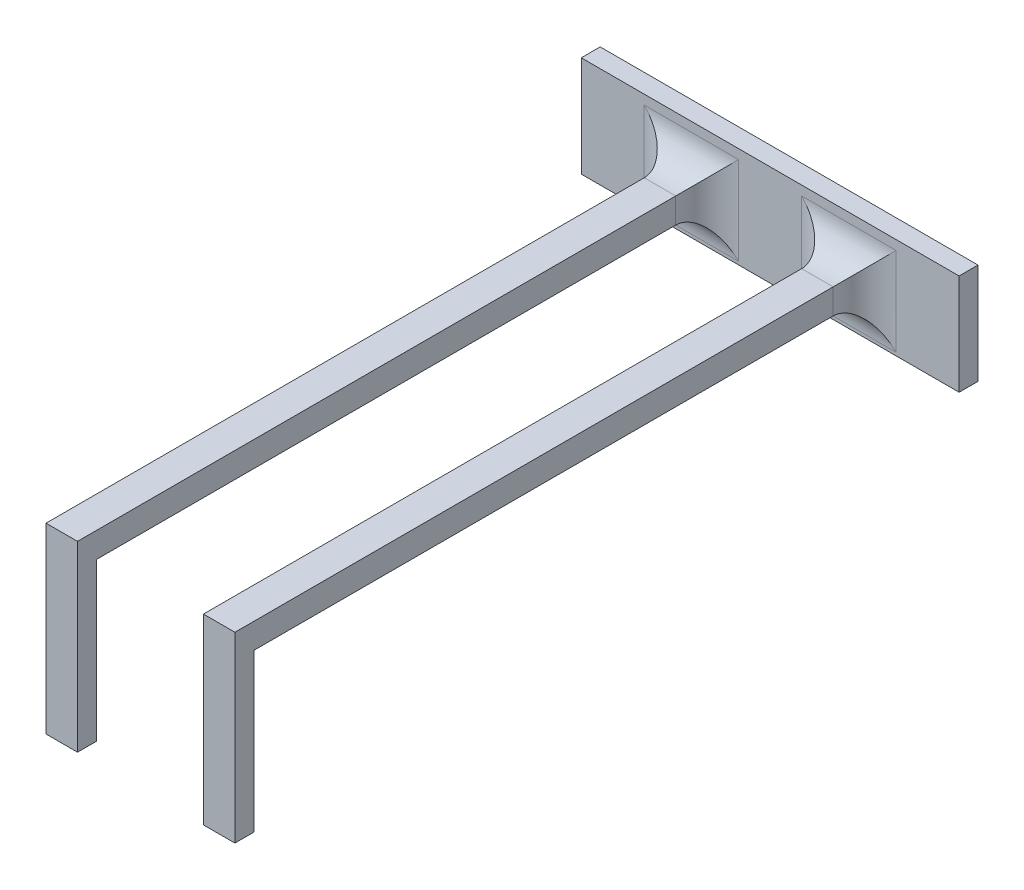
SolidWorks part; units mm, degrees
ref_plane "前视基准面" through (0, 0, 0) normal (0, 0, 1) x (1, 0, 0)
ref_plane "上视基准面" through (0, 0, 0) normal (0, 1, 0) x (1, 0, 0)
ref_plane "右视基准面" through (0, 0, 0) normal (1, 0, 0) x (0, 0, -1)
other "Configuration Table"
sketch "草图1" plane through (0, 0, 0) normal (0, 0, 1) x (1, 0, 0)
  line L1 (-22.149, 8.3709) -> (37.851, 8.3709)
  line L2 (-22.149, 8.3709) -> (-22.149, -7.6291)
  line L3 (-22.149, -7.6291) -> (37.851, -7.6291)
  line L4 (37.851, 8.3709) -> (37.851, -7.6291)
  dimension "D1" = 60
  dimension "D2" = 16
extrude "凸台-拉伸1" add sketch "草图1" along normal blind 3
sketch "草图2" plane through (0, 0, 3) normal (0, 0, 1) x (1, 0, 0)
  line L0 (-22.149, 8.3709) -> (-22.149, -7.6291) construction
  line L1 (-22.149, 1.8709) -> (37.851, 1.8709)
  line L2 (-22.149, 1.8709) -> (-22.149, -2.1291)
  line L3 (-22.149, -2.1291) -> (37.851, -2.1291)
  line L4 (37.851, 1.8709) -> (37.851, -2.1291)
  line L5 (37.851, -7.6291) -> (37.851, 8.3709) construction
  line L6 (-22.149, -7.6291) -> (37.851, -7.6291) construction
  dimension "D1" = 4
  dimension "D2" = 5.5
extrude "凸台-拉伸2" add sketch "草图2" along normal blind 100
sketch "草图3" plane through (0, -2.1291, 0) normal (0, -1, 0) x (1, 0, 0)
  line L0 (-22.149, 103) -> (37.851, 103) construction
  line L1 (-7.149, 103) -> (-2.149, 103)
  line L2 (-7.149, 103) -> (-7.149, 100)
  line L3 (-7.149, 100) -> (-2.149, 100)
  line L4 (22.851, 103) -> (22.851, 100)
  line L5 (-2.149, 103) -> (-2.149, 100)
  line L6 (17.851, 103) -> (17.851, 100)
  line L7 (17.851, 103) -> (22.851, 103)
  line L8 (17.851, 100) -> (22.851, 100)
  line L9 (-22.149, 103) -> (-22.149, 3) construction
  dimension "D1" = 20
  dimension "D2" = 30
  dimension "D3" = 5
  dimension "D4" = 3
  dimension "D5" = 15
extrude "凸台-拉伸3" add sketch "草图3" along normal blind 25
sketch "草图4" plane through (0, -2.1291, 0) normal (0, -1, 0) x (1, 0, 0)
  line L0 (-22.149, 3) -> (37.851, 3) construction
  line L1 (-22.149, 103) -> (-7.149, 103)
  line L2 (-22.149, 103) -> (-22.149, 3)
  line L3 (-22.149, 3) -> (-7.149, 3)
  line L4 (-7.149, 103) -> (-7.149, 3)
  line L5 (17.851, 103) -> (17.851, 100) construction
  line L6 (-2.149, 103) -> (17.851, 103)
  line L7 (-2.149, 103) -> (-2.149, 3)
  line L8 (-2.149, 3) -> (17.851, 3)
  line L9 (17.851, 103) -> (17.851, 3)
  line L10 (22.851, 103) -> (37.851, 103)
  line L11 (22.851, 103) -> (22.851, 3)
  line L12 (22.851, 3) -> (37.851, 3)
  line L13 (37.851, 103) -> (37.851, 3)
  line L14 (-7.149, 103) -> (-7.149, 100) construction
extrude "切除-拉伸1" cut sketch "草图4" against normal blind 30
fillet "圆角1" radius 5 8 edges at (20.351, 1.8709, 3) (22.851, -0.1291, 3) (20.351, -2.1291, 3) (17.851, -0.1291, 3) (-4.649, 1.8709, 3) (-2.149, -0.1291, 3) (-4.649, -2.1291, 3) (-7.149, -0.1291, 3)
